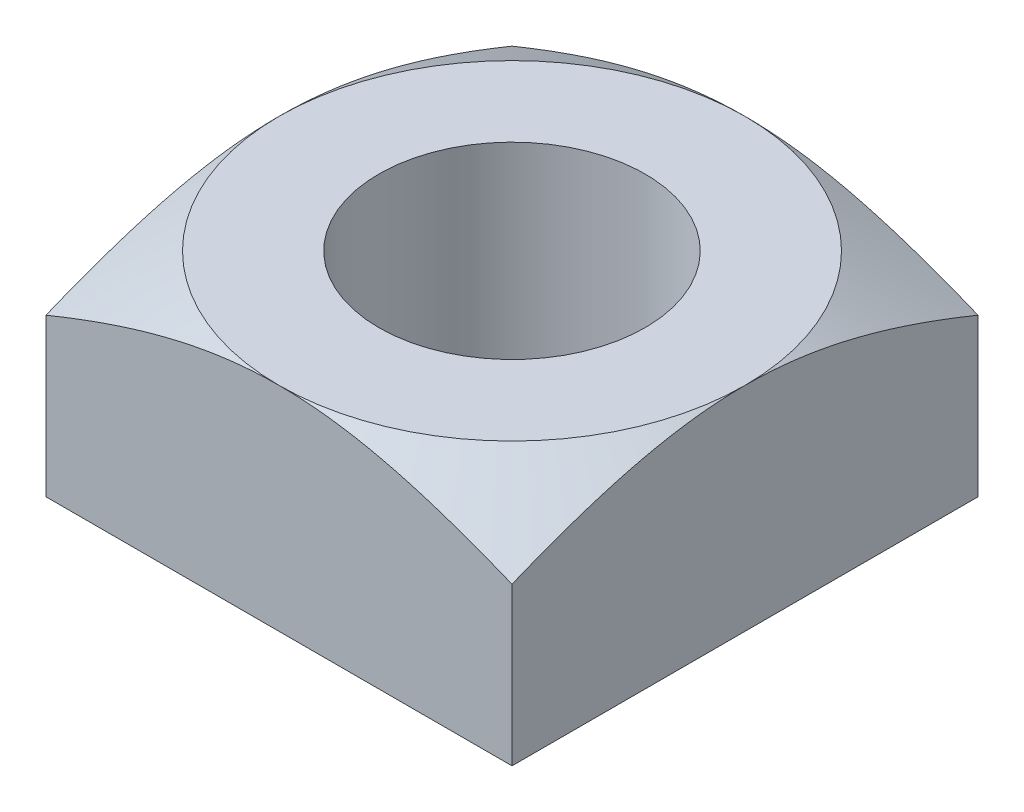
SolidWorks part; units mm, degrees
ref_plane "Front Plane" through (0, 0, 0) normal (0, 0, 1) x (1, 0, 0)
ref_plane "Top Plane" through (0, 0, 0) normal (0, 1, 0) x (1, 0, 0)
ref_plane "Right Plane" through (0, 0, 0) normal (1, 0, 0) x (0, 0, -1)
sketch "Sketch1" plane through (0, 0, 0) normal (0, 1, 0) x (1, 0, 0)
  line L1 (-3.5, 2.0207) -> (-3.5, -4.3951) construction
  line L4 (3.5, -2.0207) -> (3.5, 4.3951) construction
  line L7 (-3.5, 3.5) -> (3.5, 3.5)
  line L8 (-3.5, 3.5) -> (-3.5, -3.5)
  line L9 (-3.5, -3.5) -> (3.5, -3.5)
  line L10 (3.5, 3.5) -> (3.5, -3.5)
  line L11 (26.3103, -11.1488) -> (20.7541, -7.9409) [skipped]
  line L12 (22.8103, 17.211) -> (17.2541, 14.0031) [skipped]
  line L13 (0, -4.0415) -> (5.5562, -0.8335) [skipped]
  line L14 (-3.5, -2.0207) -> (2.0562, -5.2286) [skipped]
  circle A0 centre (0, 0) radius 3.5 construction
  circle A1 centre (0, 0) radius 2
  dimension "Thread Size" = 4
  dimension "Hex" = 7
extrude "Boss-Extrude1" add sketch "Sketch1" along normal mid plane 3.2
sketch "Sketch5" plane through (0, 1.6, 0) normal (0, 1, 0) x (1, 0, 0)
  circle A1 centre (0, 0) radius 3.5
  circle A2 centre (0, 0) radius 3.5 construction
extrude "Cut-Extrude2" cut sketch "Sketch5" against normal through all draft 60 flip side to cut
sketch "Sketch2" [suppressed] plane through (0, 1.6, 0) normal (0, 1, 0) x (1, 0, 0)
  circle A1 centre (0, 0) radius 2
  circle A3 centre (0, 0) radius 2 construction
curve "Helix/Spiral1" [suppressed] pitch 0.7 height 3.9 turns 5.5714 parameters "Pitch"=0.7
sketch "Sketch3" [suppressed] plane through (0, 0, 0) normal (1, 0, 0) x (0, 0, -1)
  line L0 (1.5453, 1.95) -> (2, 2.2125)
  line L1 (2, 2.2125) -> (2, 1.6)
  line L2 (2, 1.6) -> (1.5453, 1.8625)
  line L3 (1.5453, 1.8625) -> (1.5453, 1.95)
  line L4 (1.7727, 2.0812) -> (1.7727, 1.7312) construction
  line L5 (1.5453, 1.9062) -> (2, 1.9062) construction
  line L6 (2, 1.6) -> (-2, 1.6) construction
  dimension "D1" = 60
  dimension "D2" = 0.0875
  dimension "D3" = 0.35
sweep "Sweep1" [suppressed] add profiles "Sketch3" path "Helix/Spiral1"
sketch "Sketch4" [suppressed] plane through (0, 1.6, 0) normal (0, 1, 0) x (1, 0, 0)
  circle A1 centre (0, 0) radius 2
  circle A2 centre (0, 0) radius 2
  dimension "D1" = 0
extrude "Cut-Extrude1" [suppressed] cut sketch "Sketch4" along normal through all and the other way through all draft 45
mirror "Mirror1" [suppressed] about plane through (0, 0, 0) normal (0, 1, 0)
ref_plane "Contact Plane 1" through (0, -1.6, 0) normal (0, -1, 0) x (-1, 0, 0)
ref_axis "Center Axis 1" through (0, -2.5545, 0) along (0, 1, 0)
equation "\"D2@Sketch3\" = \"Pitch@Helix/Spiral1\"*.125"
equation "\"D3@Sketch3\" = \"Pitch@Helix/Spiral1\"*.5"
equation "\"D3@Helix/Spiral1\" = \"Height@Boss-Extrude1\"+\"Pitch@Helix/Spiral1\""
